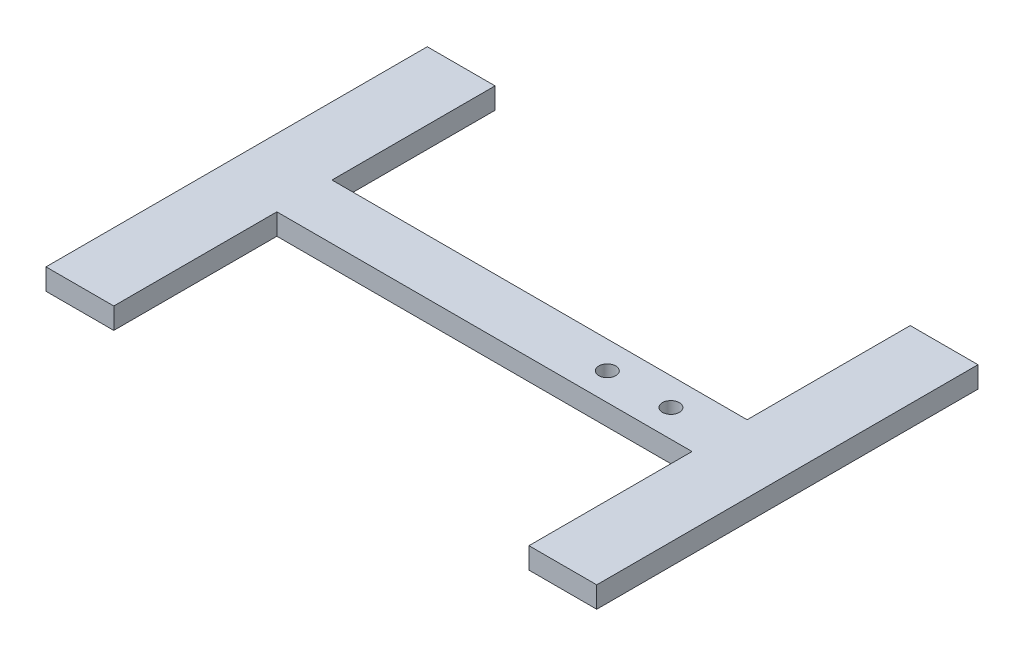
SolidWorks part; units mm, degrees
ref_plane "Front Plane" through (0, 0, 0) normal (0, 0, 1) x (1, 0, 0)
ref_plane "Top Plane" through (0, 0, 0) normal (0, 1, 0) x (1, 0, 0)
ref_plane "Right Plane" through (0, 0, 0) normal (1, 0, 0) x (0, 0, -1)
sketch "Sketch2" plane through (0, 0, 0) normal (0, 1, 0) x (1, 0, 0)
  line L1 (-65, 45) -> (65, 45)
  line L2 (-65, 45) -> (-65, -45)
  line L3 (-65, -45) -> (65, -45)
  line L4 (65, 45) -> (65, -45)
  line L5 (-65, 45) -> (65, -45) construction
  line L6 (-65, -45) -> (65, 45) construction
  point P0 (0, 0)
  dimension "D1" = 130
  dimension "D2" = 90
extrude "Boss-Extrude1" add sketch "Sketch2" along normal blind 5
sketch "Sketch3" plane through (0, 5, 0) normal (0, 1, 0) x (1, 0, 0)
  line L0 (-65, 45) -> (-65, -45) construction
  circle A0 centre (37.5, 0) radius 2
  circle A1 centre (22.5, 0) radius 2
  point P4 (0, 0)
  dimension "D1" = 15
  dimension "D2" = 102.5
extrude "Cut-Extrude1" cut sketch "Sketch3" against normal blind 5
sketch "Sketch4" plane through (0, 5, 0) normal (0, 1, 0) x (1, 0, 0)
  line L0 (65, -45) -> (65, 45) construction
  line L1 (-65, 6.5) -> (65, 6.5)
  line L2 (-65, 6.5) -> (-65, -6.5)
  line L3 (-65, -6.5) -> (65, -6.5)
  line L4 (65, 6.5) -> (65, -6.5)
  line L5 (-65, 6.5) -> (65, -6.5) construction
  line L6 (-65, -6.5) -> (65, 6.5) construction
  line L7 (-65, -45) -> (65, -45) construction
  line L8 (-65, 45) -> (-49, 45)
  line L9 (-65, 45) -> (-65, -45)
  line L10 (-65, -45) -> (-49, -45)
  line L11 (-49, 45) -> (-49, -45)
  line L12 (0, 0) -> (0, -27.2209) construction
  line L13 (65, -45) -> (49, -45)
  line L14 (49, 45) -> (49, -45)
  line L15 (65, 45) -> (49, 45)
  line L16 (65, 45) -> (65, -45)
  point P0 (0, 0)
  line M13 (65, 45) -> (-65, 45)
  line M15 (-65, -45) -> (65, -45)
  dimension "D1" = 13
  dimension "D2" = 16
extrude "Cut-Extrude2" cut sketch "Sketch4" against normal up to surface (5 mm away) contours L14 L11 L1 M13 | L14 L3 L11 M15 region at (0, 5, -25.75) region at (0, 5, 25.75) up to face at (37.5, 0, 2)
